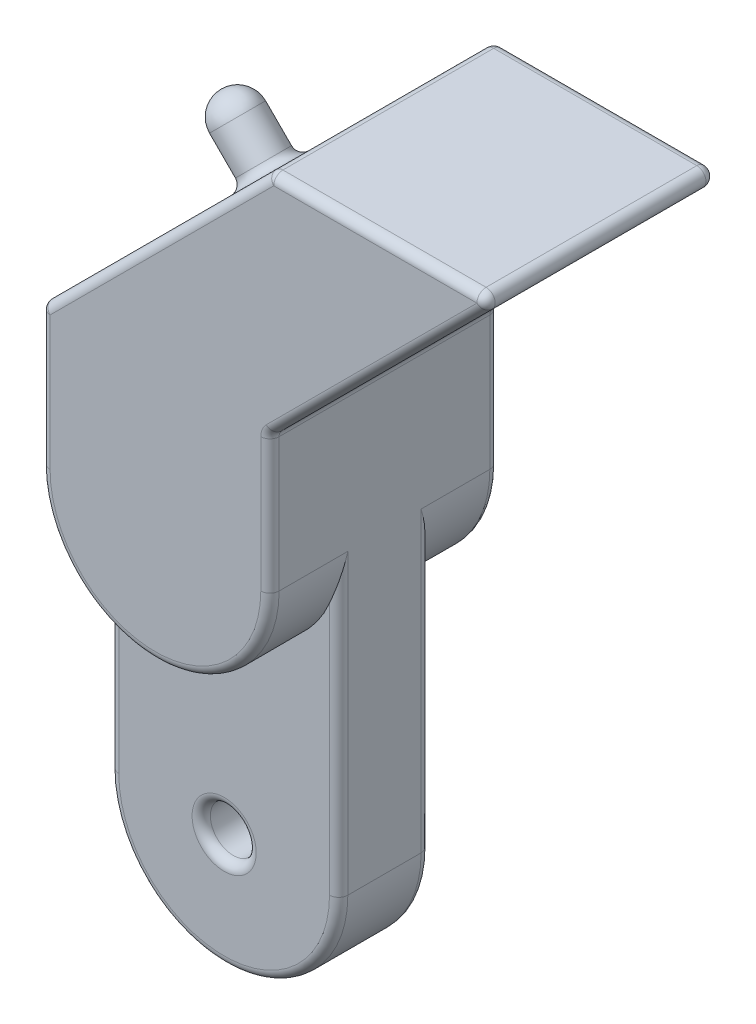
SolidWorks part; units mm, degrees
material "C-Glass Fiber"
ref_plane "Front Plane" through (0, 0, 0) normal (0, 0, 1) x (1, 0, 0)
ref_plane "Top Plane" through (0, 0, 0) normal (0, 1, 0) x (1, 0, 0)
ref_plane "Right Plane" through (0, 0, 0) normal (1, 0, 0) x (0, 0, -1)
sketch "Sketch1" plane through (0, 0, 0) normal (0, 1, 0) x (1, 0, 0)
  line L1 (-31.75, -31.75) -> (31.75, -31.75)
  line L2 (-31.75, -31.75) -> (-31.75, 31.75)
  line L3 (-31.75, 31.75) -> (31.75, 31.75)
  line L4 (31.75, -31.75) -> (31.75, 31.75)
  line L5 (-31.75, -31.75) -> (31.75, 31.75) construction
  line L6 (-31.75, 31.75) -> (31.75, -31.75) construction
  point P0 (0, 0)
  dimension "D1" = 63.5
  dimension "D2" = 63.5
extrude "Boss-Extrude1" add sketch "Sketch1" along normal blind 152.4
fillet "Fillet1" 2 edges at (-31.75, 0, 0) (31.75, 0, 0) type full round first side face at (-31.75, 76.2, 0) second side face at (31.75, 76.2, 0) middle face at (0, 0, 0)
sketch "Sketch2" plane through (0, 0, 0) normal (1, 0, 0) x (0, 0, -1)
  line L0 (-31.75, 152.4) -> (-31.75, 31.75) construction
  line L1 (-31.75, 82.55) -> (-12.7, 82.55)
  line L2 (-31.75, 82.55) -> (-31.75, 0)
  line L3 (-31.75, 0) -> (-12.7, 0)
  line L4 (-12.7, 82.55) -> (-12.7, 0)
  line L5 (-31.75, 0) -> (31.75, 0) construction
  dimension "D1" = 19.05
  dimension "D2" = 82.55
extrude "Cut-Extrude1" cut sketch "Sketch2" against normal mid plane 63.5
sketch "Sketch4" plane through (0, 0, 0) normal (0, 0, 1) x (1, 0, 0)
  line L0 (0, 152.4) -> (63.5, 215.9)
  line L1 (-31.75, 152.4) -> (31.75, 152.4) construction
  line L3 (65.0394, 152.4) -> (0, 152.4) construction
  dimension "D1" = 45
  dimension "D2" = 63.5
fillet "Fillet2" 2 edges at (31.75, 82.55, 22.225) (-31.75, 82.55, 22.225) type full round first side face at (31.75, 88.9, 4.2333) second side face at (-31.75, 88.9, 4.2333) middle face at (0, 82.55, 22.225)
mirror "Mirror1" about plane through (0, 0, 0) normal (0, 0, 1) of "Fillet2", "Cut-Extrude1"
sketch "Sketch5" plane through (0, 152.4, 0) normal (0, 1, 0) x (1, 0, 0)
  line L0 (-31.75, -31.75) -> (31.75, -31.75) construction
  line L1 (31.75, -31.75) -> (31.75, 31.75) construction
  line L2 (31.75, 31.75) -> (-31.75, 31.75) construction
  line L3 (-31.75, 31.75) -> (-31.75, -31.75) construction
  line L4 (-31.75, -31.75) -> (31.75, -31.75)
  line L5 (31.75, -31.75) -> (31.75, 31.75)
  line L6 (31.75, 31.75) -> (-31.75, 31.75)
  line L7 (-31.75, 31.75) -> (-31.75, -31.75)
sweep "Sweep1" add profiles "Sketch5" path "Sketch4"
sketch "Sketch6" plane through (0, 0, 0) normal (0, 0, 1) x (1, 0, 0)
  line L0 (0, 184.15) -> (-13.4704, 197.6204)
  line L1 (-31.75, 152.4) -> (31.75, 215.9) construction
  line L2 (-4.4901, 179.6599) -> (0, 184.15)
  line L3 (-4.4901, 179.6599) -> (-13.4704, 188.6401)
  line L4 (-13.4704, 197.6204) -> (-11.5241, 199.5667) construction
  arc A0 (-13.4704, 188.6401) -> (-13.4704, 197.6204) centre (-8.9803, 193.1303) cw
  dimension "D1" = 6.35
  dimension "D3" = 12.7
revolve "Revolve1" add sketch "Sketch6" angle 360 about L0
hole_wizard "1/2 (0.5000) Dowel Hole1" positions "Sketch7" profile "Sketch9" hole size "1/2" standard "ANSI Inch" end condition up to next
sketch "Sketch7" plane through (0, 0, 12.7) normal (0, 0, 1) x (1, 0, 0)
  point P0 (0, 31.75)
sketch "Sketch9" plane through (0, 31.75, 12.7) normal (1, 0, 0) x (0, -1, 0)
  line L0 (0, 0) -> (0, 25.4)
  line L1 (0, 25.4) -> (6.35, 25.4)
  line L2 (6.35, 25.4) -> (6.35, 0)
  line L5 (6.35, 0) -> (0, 0)
  line L11 (0, -6.35) -> (0, 107.95) construction
  dimension "Thru Hole Dia." = 12.7
  dimension "Thru Hole Depth" = 25.4
fillet "Fillet3" radius 2.54 25 edges at (63.5, 184.15, -31.75) (-31.75, 133.35, -31.75) (0, 82.55, -31.75) (-31.75, 133.35, 31.75) (0, 82.55, 31.75) (-31.75, 73.025, -12.7) (0, 0, -12.7) (-31.75, 73.025, 12.7) (31.75, 73.025, 12.7) (4.4901, 188.6401, 0) (-31.75, 152.4, 0) (0, 184.15, -31.75) (63.5, 215.9, -31.75) (31.75, 215.9, 0) (63.5, 215.9, 31.75) (95.25, 215.9, 0) (31.75, 152.4, 0) (63.5, 184.15, 31.75) (0, 184.15, 31.75) (31.75, 133.35, -31.75) (31.75, 133.35, 31.75) (0, 38.1, -12.7) (6.35, 31.75, 12.7) (31.75, 73.025, -12.7) (0, 0, 12.7)
